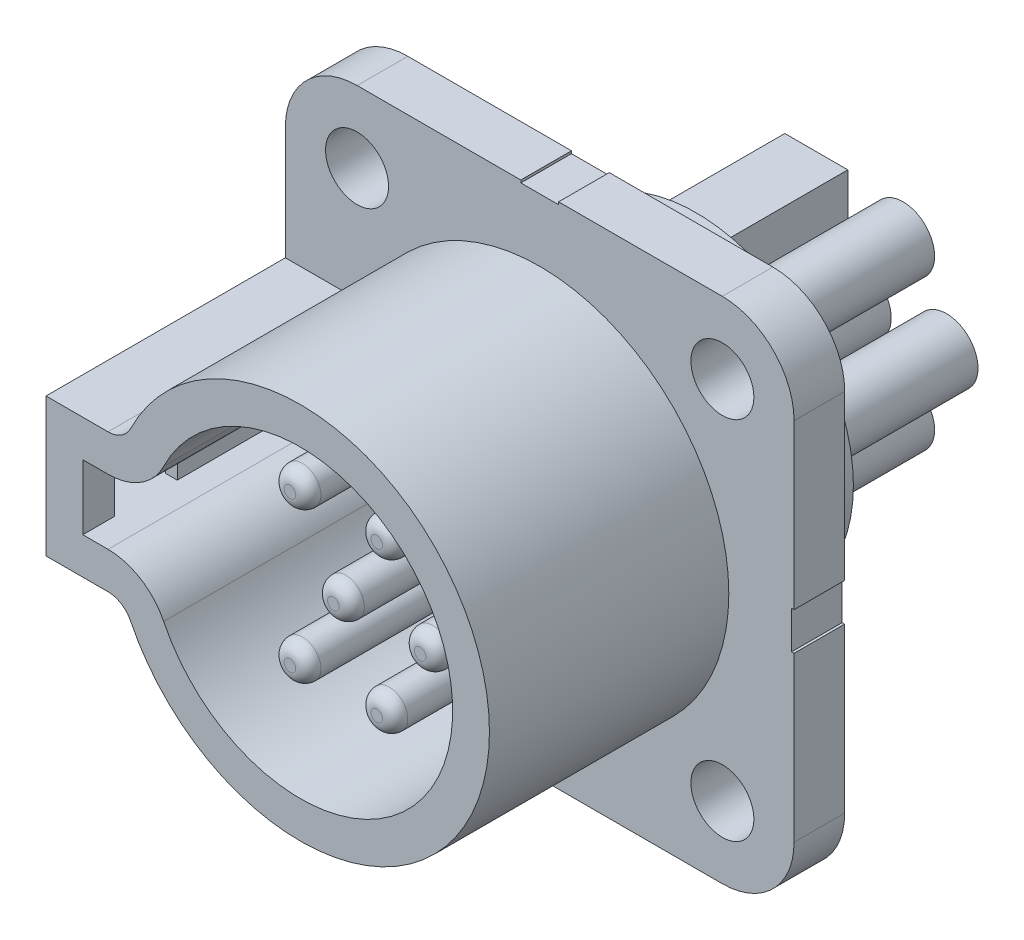
SolidWorks part; units mm, degrees
ref_plane "Front Plane" through (0, 0, 0) normal (0, 0, 1) x (1, 0, 0)
ref_plane "Top Plane" through (0, 0, 0) normal (0, 1, 0) x (1, 0, 0)
ref_plane "Right Plane" through (0, 0, 0) normal (1, 0, 0) x (0, 0, -1)
sketch "Sketch1" plane through (0, 0, 0) normal (0, 0, 1) x (1, 0, 0)
  line L1 (-10.095, 10.095) -> (10.095, 10.095)
  line L2 (-10.095, 10.095) -> (-10.095, -10.095)
  line L3 (-10.095, -10.095) -> (10.095, -10.095)
  line L4 (10.095, 10.095) -> (10.095, -10.095)
  line L5 (-10.095, 10.095) -> (10.095, -10.095) construction
  line L6 (-10.095, -10.095) -> (10.095, 10.095) construction
  point P0 (0, 0)
  dimension "D1" = 20.19
  dimension "D2" = 20.19
extrude "Boss-Extrude1" add sketch "Sketch1" along normal blind 2.01
sketch "Sketch2" plane through (0, 0, 2.01) normal (0, 0, 1) x (1, 0, 0)
  line L0 (0, 0) -> (0, 10.095) construction
  line L1 (10.095, 10.095) -> (-10.095, 10.095) construction
  line L2 (0, 0) -> (-10.095, 0) construction
  line L3 (-10.095, 10.095) -> (-10.095, -10.095) construction
  circle A0 centre (-7.25, 7.25) radius 1.25
  circle A1 centre (7.25, 7.25) radius 1.25
  circle A2 centre (7.25, -7.25) radius 1.25
  circle A3 centre (-7.25, -7.25) radius 1.25
  dimension "D1" = 2.5
  dimension "D2" = 7.25
  dimension "D3" = 7.25
extrude "Cut-Extrude1" cut sketch "Sketch2" against normal up to surface (2.01 mm away) up to face at (0, 0, 0)
fillet "Fillet1" radius 2.85 4 edges at (10.095, -10.095, 1.005) (-10.095, -10.095, 1.005) (10.095, 10.095, 1.005) (-10.095, 10.095, 1.005)
sketch "Sketch4" plane through (0, 0, 2.01) normal (0, 0, 1) x (1, 0, 0)
  line L0 (-10.095, -2.7495) -> (-10.095, 2.7495)
  line L1 (-10.095, 7.245) -> (-10.095, -7.245) construction
  line L2 (-10.095, 2.7495) -> (-7.6339, 2.7495)
  line L3 (-10.095, 0) -> (11.2357, 0) construction
  line L4 (-10.095, -2.7495) -> (-7.6339, -2.7495)
  line L5 (-8.635, -1.2895) -> (-8.635, 1.2895)
  line L6 (-8.635, 1.2895) -> (-7.6339, 1.2895)
  line L7 (-8.635, -1.2895) -> (-7.6339, -1.2895)
  line L8 (0, 10.095) -> (0, -11.6505) construction
  line L9 (7.245, 10.095) -> (-7.245, 10.095) construction
  line L10 (0, 6.045) -> (3.3385, 6.045) construction
  line L11 (0, -6.045) -> (3.3385, -6.045) construction
  line L12 (0, -7.505) -> (3.9298, -7.505) construction
  line L13 (0, 7.505) -> (4.2254, 7.505) construction
  arc A0 (-6.7363, 3.3086) -> (-6.7363, -3.3086) centre (0, 0) cw
  arc A1 (-6.7363, 3.3086) -> (-7.6339, 2.7495) centre (-7.6339, 3.7495) cw
  arc A2 (-6.7363, -3.3086) -> (-7.6339, -2.7495) centre (-7.6339, -3.7495) ccw
  arc A3 (-5.4259, 2.665) -> (-7.6339, 1.2895) centre (-7.6339, 3.7495) cw
  arc A4 (-5.4259, 2.665) -> (-5.4259, -2.665) centre (0, 0) cw
  arc A5 (-5.4259, -2.665) -> (-7.6339, -1.2895) centre (-7.6339, -3.7495) ccw
  dimension "D1" = 1
  dimension "D3" = 15.01
  dimension "D4" = 12.09
extrude "Boss-Extrude2" add sketch "Sketch4" along normal blind 9.5
sketch "Sketch5" plane through (-10.095, 0, 0) normal (-1, 0, 0) x (0, 0, 1)
  line L0 (0, 7.245) -> (0, -7.245) construction
  line L1 (0, 1.2895) -> (10.26, 1.2895)
  line L2 (0, 1.2895) -> (0, -1.2895)
  line L3 (0, -1.2895) -> (10.26, -1.2895)
  line L4 (10.26, 1.2895) -> (10.26, -1.2895)
  line L6 (0, 0) -> (-1.0293, 0) construction
  line L7 (11.51, 2.7495) -> (11.51, -2.7495) construction
  line L8 (11.51, 2.7495) -> (2.01, 2.7495) construction
  line L9 (11.51, -2.7495) -> (2.01, -2.7495) construction
  dimension "D1" = 1.25
  dimension "D2" = 1.46
  dimension "D3" = 1.46
extrude "Cut-Extrude2" cut sketch "Sketch5" against normal blind 1
sketch "Sketch6" plane through (-9.095, 0, 0) normal (-1, 0, 0) x (0, 0, 1)
  line L0 (0, -1.2895) -> (10.26, -1.2895) construction
  line L1 (10.26, 1.2895) -> (7.76, 1.2895)
  line L2 (10.26, 1.2895) -> (10.26, -1.2895)
  line L3 (10.26, -1.2895) -> (7.76, -1.2895)
  line L4 (7.76, 1.2895) -> (7.76, -1.2895)
  dimension "D1" = 2.5
extrude "Cut-Extrude3" cut sketch "Sketch6" against normal up to next
sketch "Sketch7" plane through (0, 0, 0) normal (0, 0, -1) x (-1, 0, 0)
  circle A0 centre (0, 0) radius 6.25
  dimension "D1" = 12.5
extrude "Boss-Extrude3" add sketch "Sketch7" along normal blind 4.19
sketch "Sketch8" plane through (0, 0, 2.01) normal (0, 0, 1) x (1, 0, 0)
  line L0 (-3.445, 0) -> (5.0962, 0) construction
  circle A0 centre (0, 0) radius 0.73
  circle A2 centre (3.445, 0) radius 0.73
  circle A3 centre (1.7225, 2.9835) radius 0.73
  circle A4 centre (-1.7225, 2.9835) radius 0.73
  circle A5 centre (1.7225, -2.9835) radius 0.73
  circle A6 centre (-1.7225, -2.9835) radius 0.73
  dimension "D1" = 1.46
extrude "Boss-Extrude4" add sketch "Sketch8" along normal blind 8.19 and the other way blind 7
fillet "Fillet2" radius 0.5 6 edges at (-2.4525, -2.9835, 10.2) (2.4525, 2.9835, 10.2) (0.9925, -2.9835, 10.2) (4.175, 0, 10.2) (0.73, 0, 10.2) (-0.9925, 2.9835, 10.2)
sketch "Sketch9" plane through (0, 0, -4.19) normal (0, 0, -1) x (-1, 0, 0)
  line L0 (2.7225, 2.9835) -> (2.7225, 4.3134) construction
  line L1 (1.7225, 3.9835) -> (2.7225, 3.9835) construction
  line L2 (0, 0) -> (6.9156, 0) construction
  line L3 (0.7225, 1.9835) -> (2.7225, 1.9835)
  line L4 (0.7225, 1.9835) -> (0.7225, 3.9835)
  line L5 (0.7225, 3.9835) -> (2.7225, 3.9835)
  line L6 (2.7225, 1.9835) -> (2.7225, 3.9835)
  line L7 (0.7225, 1.9835) -> (2.7225, 3.9835) construction
  line L8 (0.7225, 3.9835) -> (2.7225, 1.9835) construction
  line L9 (0.7225, -3.9835) -> (2.7225, -3.9835)
  line L10 (0.7225, -1.9835) -> (0.7225, -3.9835)
  line L11 (2.7225, -1.9835) -> (2.7225, -3.9835)
  line L12 (0.7225, -1.9835) -> (2.7225, -1.9835)
  circle A0 centre (-1.7225, 2.9835) radius 1
  circle A2 centre (0, 0) radius 1
  circle A3 centre (-3.445, 0) radius 1
  circle A4 centre (-1.7225, -2.9835) radius 1
  circle A5 centre (-1.7225, -2.9835) radius 1
  point P0 (-1.7225, 2.9835)
  point P1 (1.7225, 2.9835)
  point P3 (-3.445, 0)
  point P5 (0, 0)
  point P7 (-1.7225, -2.9835)
  point P9 (1.7225, -2.9835)
  dimension "D1" = 2
  dimension "D2" = 2
  dimension "D3" = 2
  dimension "D5" = 2
  dimension "D4" = 2.9835
  dimension "D6" = 2
extrude "Extrude-Thin1" add sketch "Sketch9" along normal blind 6.5 thin contours A0 | A2 | A3 | A4 | L9 L11 L12 L10 | L3 L6 L5 L4 thin type one direction wall 0.25
sketch "Sketch10" plane through (0, 10.095, 0) normal (0, 1, 0) x (1, 0, 0)
  line L0 (7.245, 0) -> (-7.245, 0) construction
  line L1 (-0.75, 0) -> (0.75, 0)
  line L2 (-0.75, 0) -> (-0.75, -2.01)
  line L3 (-0.75, -2.01) -> (0.75, -2.01)
  line L4 (0.75, 0) -> (0.75, -2.01)
  line L5 (7.245, -2.01) -> (-7.245, -2.01) construction
  line L6 (0, 4.99) -> (0, -4.274) construction
  line L7 (0.73, 4.99) -> (-0.73, 4.99) construction
  point P10 (0, -2.01)
  dimension "D1" = 1.5
  dimension "D2" = 0
extrude "Cut-Extrude4" cut sketch "Sketch10" against normal blind 0.1
sketch "Sketch12" plane through (10.095, 0, 0) normal (1, 0, 0) x (0, 0, -1)
  line L0 (-11.51, 0) -> (5.9037, 0)
  line L1 (-11.51, 7.505) -> (-11.51, -7.505) construction
  line L2 (0, -7.245) -> (0, 7.245) construction
  line L3 (-2.01, 0.75) -> (0, 0.75)
  line L4 (-2.01, 0.75) -> (-2.01, -0.75)
  line L5 (-2.01, -0.75) -> (0, -0.75)
  line L6 (0, 0.75) -> (0, -0.75)
  line L7 (-2.01, 0.75) -> (0, -0.75) construction
  line L8 (-2.01, -0.75) -> (0, 0.75) construction
  line L9 (-2.01, -7.245) -> (-2.01, 7.245) construction
  point P5 (-1.005, 0)
  dimension "D1" = 1.5
extrude "Cut-Extrude5" cut sketch "Sketch12" against normal blind 0.1 contours L4 L5 L6 L3
equation "\"D2@Sketch1\"=\"D1@Sketch1\""
equation "\"D3@Sketch5\"=\"D2@Sketch5\""
equation "\"D2@Sketch9\"=\"D1@Sketch9\""
equation "\"D3@Sketch9\"=\"D1@Sketch9\""
equation "\"D5@Sketch9\"=\"D1@Sketch9\""
